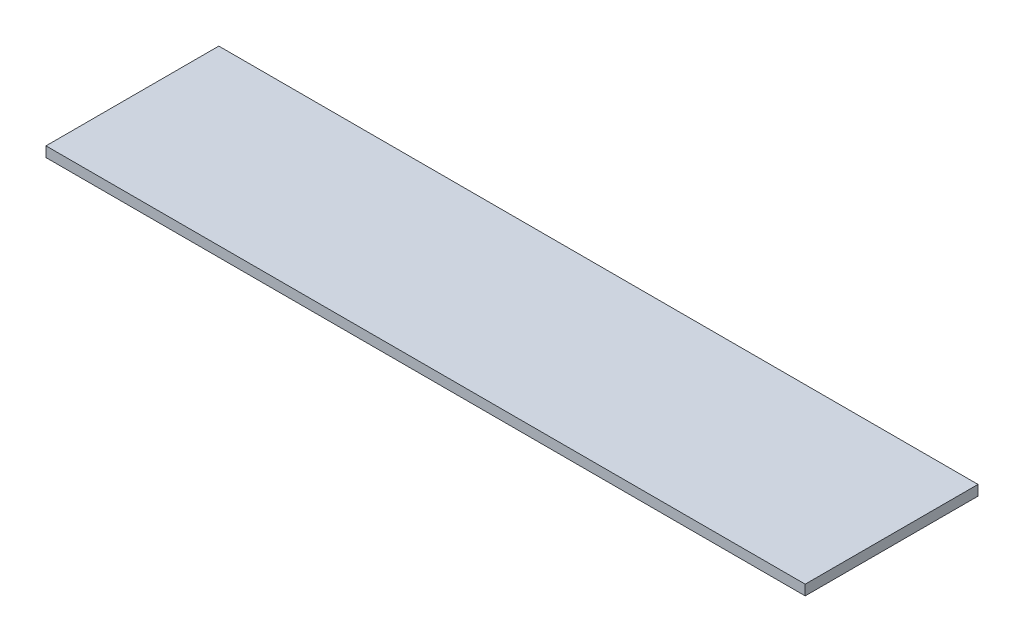
SolidWorks part; units mm, degrees
ref_plane "Спереди" through (0, 0, 0) normal (0, 0, 1) x (1, 0, 0)
ref_plane "Сверху" through (0, 0, 0) normal (0, 1, 0) x (1, 0, 0)
ref_plane "Справа" through (0, 0, 0) normal (1, 0, 0) x (0, 0, -1)
sketch "Эскиз1" plane through (0, 0, 0) normal (0, 1, 0) x (1, 0, 0)
  line L1 (-67, 15.25) -> (67, 15.25)
  line L2 (-67, 15.25) -> (-67, -15.25)
  line L3 (-67, -15.25) -> (67, -15.25)
  line L4 (67, 15.25) -> (67, -15.25)
  line L5 (-67, 15.25) -> (67, -15.25) construction
  line L6 (-67, -15.25) -> (67, 15.25) construction
  point P0 (0, 0)
  dimension "D1" = 134
  dimension "D2" = 30.5
extrude "Бобышка-Вытянуть1" add sketch "Эскиз1" along normal mid plane 1.8
